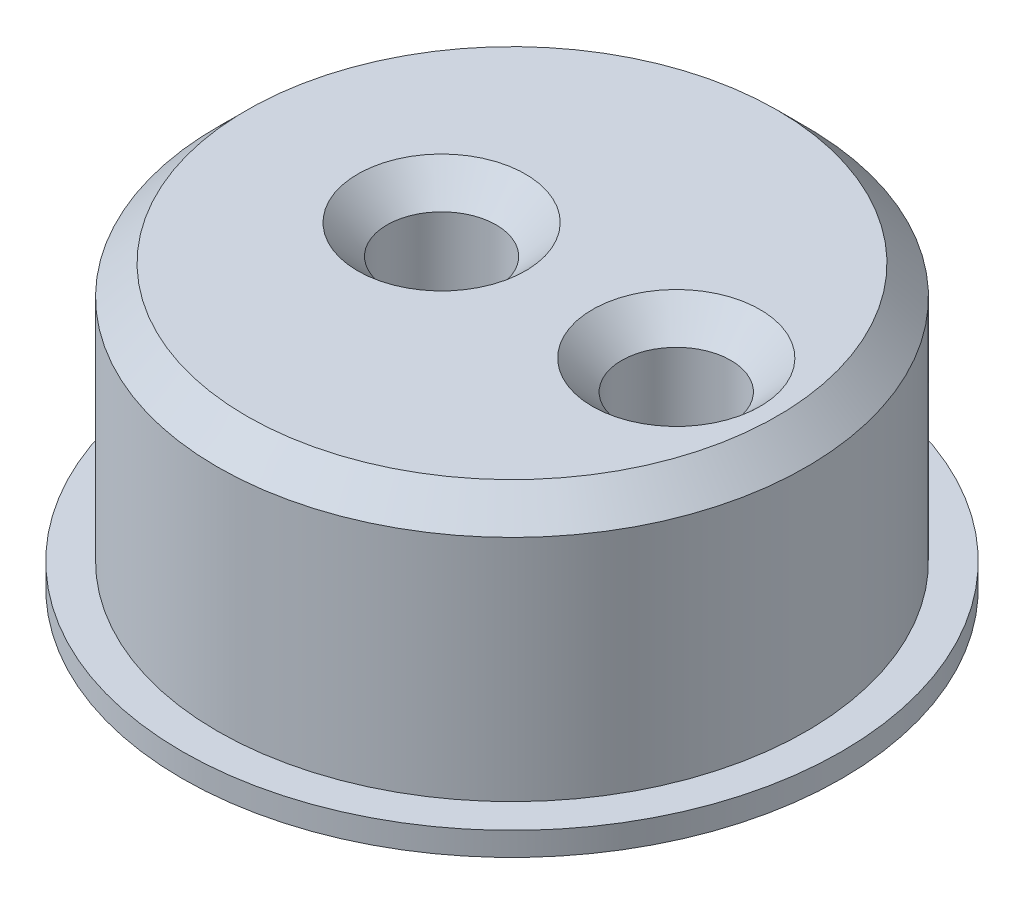
SolidWorks part; units mm, degrees
ref_plane "前视基准面" through (0, 0, 0) normal (0, 0, 1) x (1, 0, 0)
ref_plane "上视基准面" through (0, 0, 0) normal (0, 1, 0) x (1, 0, 0)
ref_plane "右视基准面" through (0, 0, 0) normal (1, 0, 0) x (0, 0, -1)
other "Configuration Table"
sketch "草图1" plane through (0, 0, 0) normal (0, 1, 0) x (1, 0, 0)
  line L0 (0.8, 6.4178) -> (0.8, -6.4114) construction
  line L1 (-5.7349, 0) -> (5.8104, 0) construction
  circle A0 centre (0, 0) radius 5.02
  circle A1 centre (2.8, 0) radius 0.93
  circle A2 centre (-1.2, 0) radius 0.93
  dimension "D1" = 10.04
  dimension "D3" = 4
  dimension "D4" = 1.86
  dimension "D2" = 0.8
extrude "凸台-拉伸1" add sketch "草图1" along normal blind 4.4
sketch "草图3" plane through (0, 0, 0) normal (0, -1, 0) x (1, 0, 0)
  circle A0 centre (2.8, 0) radius 0.93 construction
  circle A1 centre (0, 0) radius 5.02 construction
  circle A3 centre (-1.2, 0) radius 0.93 construction
  circle A4 centre (2.8, 0) radius 0.93
  circle A5 centre (-1.2, 0) radius 0.93
  circle A6 centre (0, 0) radius 5.02 construction
  circle A7 centre (0, 0) radius 5.62
  dimension "D1" = 0.6
extrude "凸台-拉伸2" add sketch "草图3" along normal blind 0.4
chamfer "倒角1" distance 0.5 angle 45 5 edges at (0, 4.4, 5.02) (-1.2, 4.4, -0.93) (2.8, 4.4, 0.93) (-1.2, -0.4, -0.93) (2.8, -0.4, -0.93)
ref_axis "基准轴1" through (0, 3.9, 0) along (0, -1, 0)
sketch "草图2" plane through (0, 0, 0) normal (0, 1, 0) x (1, 0, 0)
  line L0 (-5.9042, 0) -> (6.2358, 0) construction
